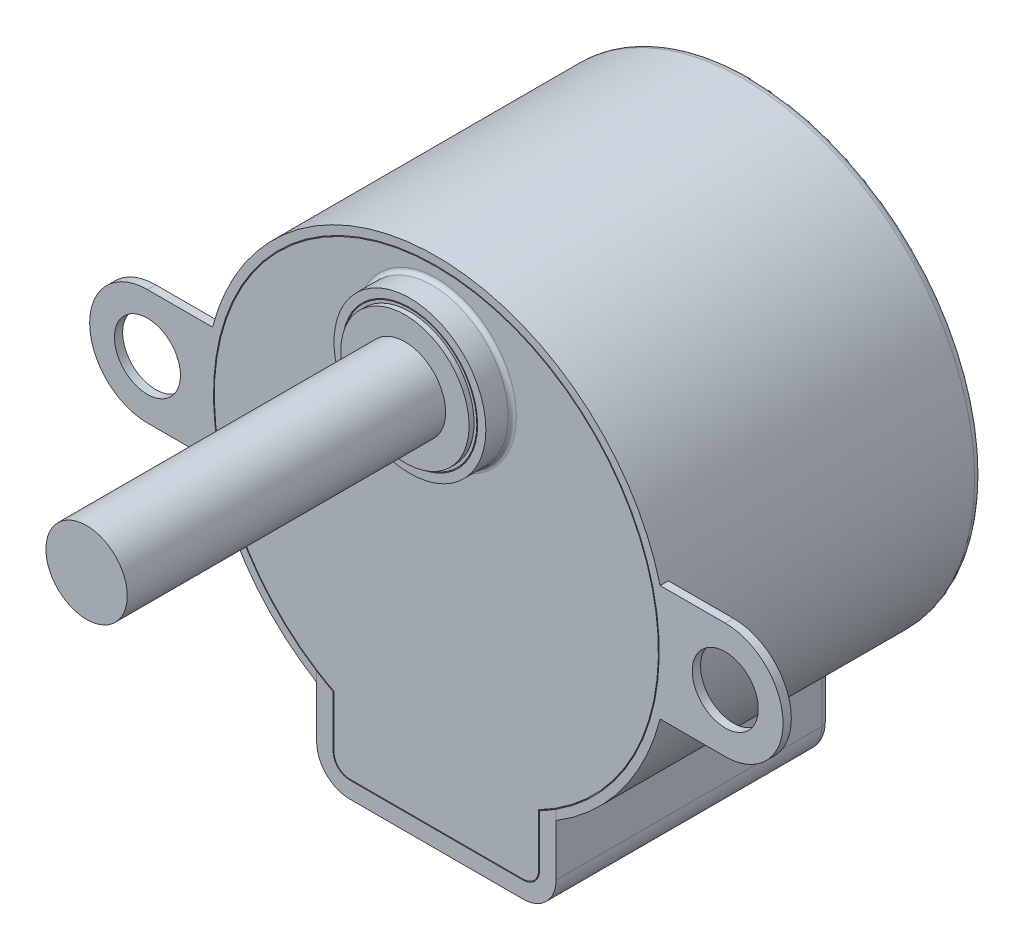
SolidWorks part; units mm, degrees
material "Chrome Stainless Steel"
ref_plane "Alzado" through (0, 0, 0) normal (0, 0, 1) x (1, 0, 0)
ref_plane "Planta" through (0, 0, 0) normal (0, 1, 0) x (1, 0, 0)
ref_plane "Vista lateral" through (0, 0, 0) normal (1, 0, 0) x (0, 0, -1)
sketch "Croquis1" plane through (0, 0, 0) normal (0, 0, 1) x (1, 0, 0)
  circle A0 centre (0, 0) radius 14
  dimension "D1" = 28
extrude "Saliente-Extruir1" add sketch "Croquis1" against normal blind 19.1
sketch "Croquis2" plane through (0, 0, 0) normal (0, 0, 1) x (1, 0, 0)
  line L0 (-13.5554, 3.5) -> (-17.5, 3.5)
  line L1 (-17.5, -3.5) -> (-13.5554, -3.5)
  line L2 (0, 0) -> (0, 3.9446) construction
  circle A0 centre (-17.5, 0) radius 2
  arc A1 (-17.5, 3.5) -> (-17.5, -3.5) centre (-17.5, 0) ccw
  arc A2 (-13.5554, 3.5) -> (-13.5554, -3.5) centre (0, 0) ccw
  circle A3 centre (0, 0) radius 14 construction
  dimension "D1" = 35
  dimension "D2" = 3.5
  dimension "D3" = 4
extrude "Saliente-Extruir2" add sketch "Croquis2" against normal blind 0.5
mirror "Simetría1" about plane through (0, 0, 0) normal (1, 0, 0) of "Saliente-Extruir2"
sketch "Croquis3" plane through (0, 0, 0) normal (0, 0, 1) x (1, 0, 0)
  circle A0 centre (0, 0) radius 13.5
  arc A1 (13.5554, 3.5) -> (-13.5554, 3.5) centre (0, 0) ccw construction
  dimension "D1" = 0.5
split line "Línea de partición1"
sketch "Croquis4" plane through (0, 0, 0) normal (0, 0, 1) x (1, 0, 0)
  line L0 (0, -11.388) -> (0, 0) construction
  line L1 (-7.25, -11.388) -> (7.25, -11.388) construction
  line L2 (-7.25, -11.388) -> (-7.25, -18.3526)
  line L3 (-7.25, -18.3526) -> (7.25, -18.3526)
  line L4 (7.25, -11.388) -> (7.25, -18.3526)
  circle A0 centre (0, 0) radius 13.5 construction
  arc A1 (-7.25, -11.388) -> (7.25, -11.388) centre (0, 0) ccw
  dimension "D1" = 14.5
extrude "Cortar-Extruir1" cut sketch "Croquis4" against normal blind 16.6
sketch "Croquis5" plane through (0, 0, 0) normal (0, 0, 1) x (1, 0, 0)
  line L0 (-7.25, -11.388) -> (-7.25, -17.1)
  line L1 (-7.25, -17.1) -> (7.25, -17.1)
  line L2 (7.25, -17.1) -> (7.25, -11.388)
  arc A0 (-7.25, -11.388) -> (7.25, -11.388) centre (0, 0) ccw
  arc A1 (7.25, -11.388) -> (-7.25, -11.388) centre (0, 0) ccw construction
  arc A2 (17.5, -3.5) -> (17.5, 3.5) centre (17.5, 0) ccw construction
  dimension "D1" = 17.1
extrude "Saliente-Extruir3" add sketch "Croquis5" against normal up to surface (16.6 mm away) separate body up to face at (0, -12.7161, -16.6)
fillet "Redondeo1" radius 2 2 edges at (7.25, -17.1, -8.3) (-7.25, -17.1, -8.3)
sketch "Croquis6" plane through (0, 0, 0) normal (0, 0, 1) x (1, 0, 0)
  line L0 (-6.25, -11.388) -> (-6.25, -15.1)
  line L1 (-5.25, -16.1) -> (5.25, -16.1)
  line L2 (6.25, -15.1) -> (6.25, -11.388)
  line L3 (-5.25, -17.1) -> (5.25, -17.1)
  line L4 (7.25, -15.1) -> (7.25, -11.388)
  line L5 (-7.25, -11.388) -> (-7.25, -15.1)
  line L6 (-5.25, -17.1) -> (5.25, -17.1)
  line L7 (7.25, -15.1) -> (7.25, -11.388)
  line L8 (-7.25, -11.388) -> (-7.25, -15.1)
  line L9 (-6.25, -11.388) -> (6.25, -11.388)
  arc A0 (-6.25, -15.1) -> (-5.25, -16.1) centre (-5.25, -15.1) ccw
  arc A1 (5.25, -16.1) -> (6.25, -15.1) centre (5.25, -15.1) ccw
  arc A3 (5.25, -17.1) -> (7.25, -15.1) centre (5.25, -15.1) ccw
  arc A4 (-7.25, -11.388) -> (7.25, -11.388) centre (0, 0) ccw
  arc A5 (-7.25, -15.1) -> (-5.25, -17.1) centre (-5.25, -15.1) ccw
  arc A6 (5.25, -17.1) -> (7.25, -15.1) centre (5.25, -15.1) ccw
  arc A7 (-7.25, -11.388) -> (7.25, -11.388) centre (0, 0) ccw construction
  arc A8 (-7.25, -15.1) -> (-5.25, -17.1) centre (-5.25, -15.1) ccw
  arc M10 (7.25, -11.388) -> (-7.25, -11.388) centre (0, 0) cw
  dimension "D1" = 0
  dimension "D2" = 1
extrude "Cortar-Extruir2" cut sketch "Croquis6" against normal blind 1 contours L1 A1 L2 L0 A0 M10 region at (0, -14.5021, 0)
extrude "Saliente-Extruir4" add sketch "Croquis6<3>" against normal blind 0.5 contours L1 A1 L2 L0 A0 M10 region at (0, -14.5021, 0)
sketch "Croquis6<3>" plane through (0, 0, 0) normal (0, 0, 1) x (1, 0, 0) same geometry as "Croquis6"
fillet "Redondeo2" radius 0.5 1 edges at (14, 0, -19.1)
sketch "Croquis7" plane through (0, 0, 0) normal (0, 0, 1) x (1, 0, 0)
  circle A0 centre (0, 8) radius 4.6
  dimension "D1" = 9.2
  dimension "D2" = 8
extrude "Saliente-Extruir5" add sketch "Croquis7" along normal blind 1.6
sketch "Croquis8" plane through (0, 0, 1.6) normal (0, 0, 1) x (1, 0, 0)
  circle A0 centre (0, 8) radius 2.5
  dimension "D1" = 5
extrude "Saliente-Extruir6" [suppressed] add sketch "Croquis8" along normal blind 8.4 separate body
sketch "Croquis9" [suppressed] plane through (0, 0, 10) normal (0, 0, 1) x (1, 0, 0)
  line L1 (-1.5, 10) -> (-2.5, 10)
  line L2 (-1.5, 10) -> (-1.5, 6)
  line L3 (-1.5, 6) -> (-2.5, 6)
  line L4 (-2.5, 10) -> (-2.5, 6)
  line L5 (1.5, 10) -> (2.5, 10)
  line L6 (1.5, 10) -> (1.5, 6)
  line L7 (1.5, 6) -> (2.5, 6)
  line L8 (2.5, 10) -> (2.5, 6)
  circle A0 centre (0, 8) radius 2.5 construction
  dimension "D1" = 3
extrude "Cortar-Extruir3" [suppressed] cut sketch "Croquis9" against normal blind 6
fillet "Redondeo3" radius 0.5 5 edges at (7.25, -13.244, -16.6) (6.6642, -16.5142, -16.6) (0, -17.1, -16.6) (-6.6642, -16.5142, -16.6) (-7.25, -13.244, -16.6)
fillet "Redondeo4" radius 0.25 1 edges at (4.6, 8, 0)
sketch "Croquis10" plane through (0, 0, 1.6) normal (0, 0, 1) x (1, 0, 0)
  circle A0 centre (0, 8) radius 4.1
  circle A1 centre (0, 8) radius 4.6 construction
  dimension "D1" = 0.5
split line "Línea de partición2"
sketch "Croquis11" plane through (0, 0, 0) normal (0, 0, 1) x (1, 0, 0)
  line L9 (-6.2, -11.9358) -> (-6.2, -15.1)
  line L10 (-5.25, -16.05) -> (5.25, -16.05)
  line L11 (6.2, -15.1) -> (6.2, -11.9358)
  line L12 (-6.2, -11.9358) -> (-6.2, -15.1)
  line L13 (-5.25, -16.05) -> (5.25, -16.05)
  line L14 (6.2, -15.1) -> (6.2, -11.9358)
  arc A15 (6.2, -11.9358) -> (7.2231, -11.3459) centre (0, 0) ccw
  arc A16 (7.2231, -11.3459) -> (-7.2231, -11.3459) centre (0, 0) ccw
  arc A17 (-7.2231, -11.3459) -> (-6.2, -11.9358) centre (0, 0) ccw
  arc A18 (-6.2, -15.1) -> (-5.25, -16.05) centre (-5.25, -15.1) ccw
  arc A19 (5.25, -16.05) -> (6.2, -15.1) centre (5.25, -15.1) ccw
  arc A20 (6.2, -11.9358) -> (7.2231, -11.3459) centre (0, 0) ccw
  arc A21 (7.2231, -11.3459) -> (-7.2231, -11.3459) centre (0, 0) ccw
  arc A22 (-7.2231, -11.3459) -> (-6.2, -11.9358) centre (0, 0) ccw
  arc A23 (-6.2, -15.1) -> (-5.25, -16.05) centre (-5.25, -15.1) ccw
  arc A24 (5.25, -16.05) -> (6.2, -15.1) centre (5.25, -15.1) ccw
  arc M10 (6.25, -11.9661) -> (7.25, -11.388) centre (0, 0) ccw
  arc M11 (7.25, -11.388) -> (-7.25, -11.388) centre (0, 0) ccw
  arc M12 (-7.25, -11.388) -> (-6.25, -11.9661) centre (0, 0) ccw
  line M13 (-6.25, -11.9661) -> (-6.25, -15.1)
  arc M14 (-6.25, -15.1) -> (-5.25, -16.1) centre (-5.25, -15.1) ccw
  line M15 (-5.25, -16.1) -> (5.25, -16.1)
  arc M16 (5.25, -16.1) -> (6.25, -15.1) centre (5.25, -15.1) ccw
  line M17 (6.25, -15.1) -> (6.25, -11.9661)
  dimension "D1" = 0.05
extrude "Cortar-Extruir4" cut sketch "Croquis11" against normal blind 0.1 contours A24 L13 A23 L12 A22 A21 A20 L14 M17 M10 M11 M12 M13 M14 M15 M16 region at (6.2099, -13.533, 0)
sketch "Croquis12" plane through (0, 0, 1.6) normal (0, 0, 1) x (1, 0, 0)
  circle A3 centre (0, 8) radius 4.05
  circle A4 centre (0, 8) radius 4.05
  circle M2 centre (0, 8) radius 4.1
  dimension "D1" = 0.05
extrude "Cortar-Extruir5" cut sketch "Croquis12" against normal blind 0.1 contours A4 M2 region at (-4.0884, 8, 1.6)
sketch "Croquis14" plane through (0, 0, -19.1) normal (0, 0, -1) x (-1, 0, 0)
  line L0 (-12.5, 1.5) -> (12.5, 1.5) construction
  line L1 (0, 1.5) -> (0, 0) construction
  line L2 (-7.5, -5) -> (7.5, -5) construction
  line L3 (0, 0) -> (0, -5) construction
  text T0 "28BYJ-48" font "Century Gothic" height 3.5
  text T1 "5V - DC" font "Century Gothic" height 2
  dimension "D1" = 25
  dimension "D2" = 1.5
  dimension "D3" = 15
  dimension "D4" = 5
extrude "Saliente-Extruir7" add sketch "Croquis14" along normal blind 0.1 separate body
chamfer "Chaflán1" [suppressed] distance 0.5 angle 45
sketch "Sketch1" plane through (0, 0, 1.6) normal (0, 0, 1) x (1, 0, 0)
  circle A0 centre (0, 8) radius 2.4638
  circle A1 centre (0, 8) radius 3.8862
  dimension "D1" = 4.9276
  dimension "D2" = 7.7724
extrude "Boss-Extrude2" add sketch "Sketch1" along normal offset from surface (19.5844 mm away) 40.2844 contours A0 region at (0, 8, 1.6) up to face at (13.5, 0, -19.1)
extrude "Boss-Extrude3" add sketch "Sketch1<4>" along normal blind 0.3048
sketch "Sketch1<4>" plane through (0, 0, 1.6) normal (0, 0, 1) x (1, 0, 0) same geometry as "Sketch1"
